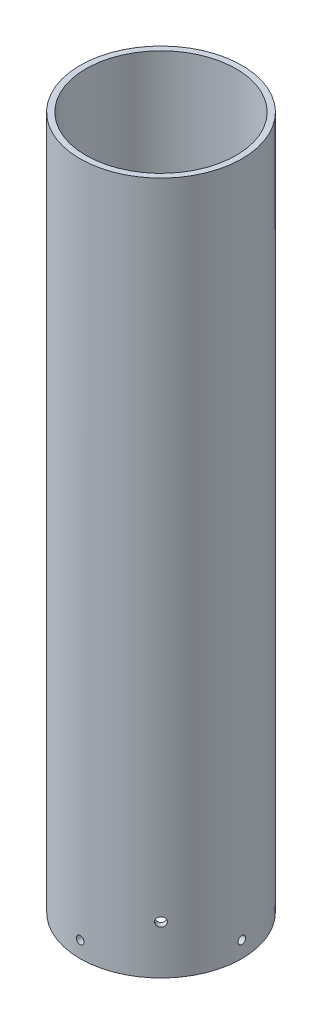
SolidWorks part; units mm, degrees
material "ПВХ 0.007 Смягченный"
ref_plane "Спереди" through (0, 0, 0) normal (0, 0, 1) x (1, 0, 0)
ref_plane "Сверху" through (0, 0, 0) normal (0, 1, 0) x (1, 0, 0)
ref_plane "Справа" through (0, 0, 0) normal (1, 0, 0) x (0, 0, -1)
sketch "Эскиз1" plane through (0, 0, 0) normal (0, 1, 0) x (1, 0, 0)
  circle A0 centre (0, 0) radius 25
  circle A1 centre (0, 0) radius 23.2
  dimension "ExDBody" = 50
  dimension "InDBody" = 46.4
extrude "Бобышка-Вытянуть1" add sketch "Эскиз1" along normal blind 214
sketch "Эскиз5" plane through (0, 0, 0) normal (0, 0, 1) x (1, 0, 0)
  circle A0 centre (0, 5) radius 1.2
  dimension "D1" = 2.4
  dimension "D2" = 5
extrude "Вырез-Вытянуть5" cut sketch "Эскиз5" against normal through all
pattern_circular "Круговой массив1" count 4 over 360 about axis through (0, 214, 0) along (0, -1, 0) of "Вырез-Вытянуть5" reverse direction yes
ref_plane "Плоскость1" through (0, 0, 0) normal (-0.7071, 0, 0.7071) x (0, -1, 0)
sketch "Эскиз6" plane through (0, 0, 0) normal (-0.7071, 0, 0.7071) x (0, -1, 0)
  line L0 (-214, 0) -> (0, 0) construction
  line L1 (0, -25) -> (0, 25) construction
  circle A0 centre (-15, 0) radius 1.4
  dimension "D1" = 15
extrude "Вырез-Вытянуть6" cut sketch "Эскиз6" against normal through all
pattern_circular "Круговой массив2" count 4 over 360 about axis through (0, 214, 0) along (0, -1, 0) of "Вырез-Вытянуть6"
